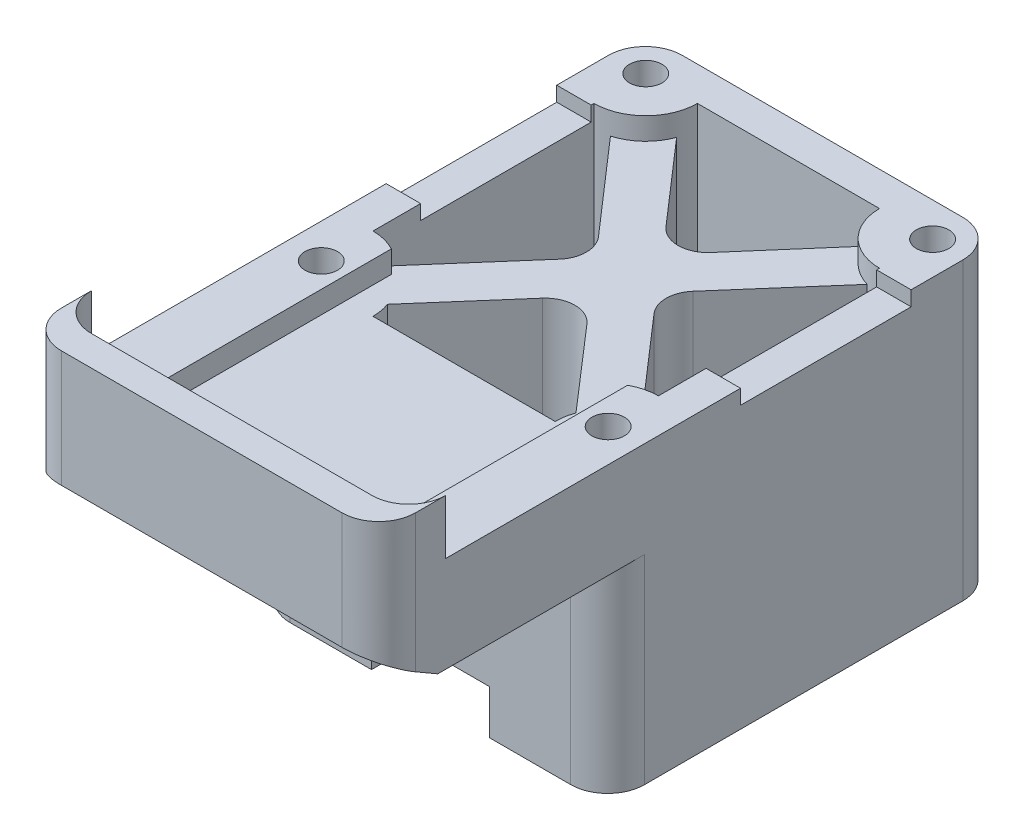
SolidWorks part; units mm, degrees
ref_plane "前视基准面" through (0, 0, 0) normal (0, 0, 1) x (1, 0, 0)
ref_plane "上视基准面" through (0, 0, 0) normal (0, 1, 0) x (1, 0, 0)
ref_plane "右视基准面" through (0, 0, 0) normal (1, 0, 0) x (0, 0, -1)
sketch "草图1" plane through (0, 0, 0) normal (0, 1, 0) x (1, 0, 0)
  line L0 (-18.2675, -0.0029) -> (18.255, -0.0029) construction
  line L2 (-9.5062, 13.2897) -> (9.4938, 13.2897)
  line L4 (-7.4272, 10.9831) -> (-1.4996, 4.1802)
  line L6 (-9.6723, 8.738) -> (-3.2009, 1.311)
  line L7 (-12.0062, 10.7897) -> (-12.0062, -10.7623)
  line L8 (-9.5062, -13.2623) -> (9.4938, -13.2623)
  line L9 (11.9938, 10.7897) -> (11.9938, -10.7623)
  line L10 (-12.0062, 13.2897) -> (11.9938, -13.2623) construction
  line L11 (-12.0062, -13.2623) -> (11.9938, 13.2897) construction
  line L12 (-9.6723, -8.7438) -> (-9.6723, 8.738)
  line L13 (-9.6723, -8.7438) -> (-3.2009, -1.3168)
  line L21 (-0.0062, -0.0029) -> (-0.0062, 21.7953) construction
  line L22 (-7.4272, 10.9831) -> (7.4147, 10.9831)
  line L23 (1.5194, 4.1838) -> (7.4147, 10.9831)
  line L24 (9.6598, -8.7438) -> (9.6598, 8.738)
  line L25 (9.6598, -8.7438) -> (3.1884, -1.3168)
  line L26 (9.6598, 8.738) -> (3.1884, 1.311)
  line L27 (1.5194, -4.1897) -> (7.4147, -10.9889)
  line L28 (-7.4272, -10.9889) -> (-1.4996, -4.186)
  line L29 (-7.4272, -10.9889) -> (7.4147, -10.9889)
  circle A0 centre (-9.6723, 10.9831) radius 1.1
  circle A1 centre (-9.6723, 10.9831) radius 2.2451
  circle A2 centre (9.7557, 10.9831) radius 1.1
  circle A4 centre (-9.6723, -10.9889) radius 1.1
  circle A5 centre (9.7557, -10.9889) radius 1.1
  circle A7 centre (-9.6723, -10.9889) radius 2.2451
  arc A8 (-12.0062, -10.7623) -> (-9.5062, -13.2623) centre (-9.5062, -10.7623) ccw
  arc A9 (9.4938, -13.2623) -> (11.9938, -10.7623) centre (9.4938, -10.7623) ccw
  arc A10 (11.9938, 10.7897) -> (9.4938, 13.2897) centre (9.4938, 10.7897) ccw
  arc A11 (-9.5062, 13.2897) -> (-12.0062, 10.7897) centre (-9.5062, 10.7897) ccw
  arc A12 (-3.2009, -1.3168) -> (-3.2009, 1.311) centre (-4.7088, -0.0029) ccw
  arc A16 (-6.1723, 10.9831) -> (-9.6723, 7.4831) centre (-9.6723, 10.9831) cw
  circle A17 centre (9.6598, 10.9831) radius 2.2451
  circle A18 centre (9.6598, -10.9889) radius 2.2451
  arc A19 (1.5194, 4.1838) -> (-1.4996, 4.1802) centre (0.0083, 5.494) cw
  arc A20 (3.1884, -1.3168) -> (3.1884, 1.311) centre (4.6963, -0.0029) cw
  arc A21 (1.5194, -4.1897) -> (-1.4996, -4.186) centre (0.0083, -5.4998) ccw
  arc A22 (6.1598, 10.9831) -> (9.6598, 7.4831) centre (9.6598, 10.9831) ccw
  arc A23 (6.1598, -10.9889) -> (9.6598, -7.4889) centre (9.6598, -10.9889) cw
  arc A24 (-6.1723, -10.9889) -> (-9.6723, -7.4889) centre (-9.6723, -10.9889) ccw
  point P5 (-0.0062, 0.0137)
  dimension "D5" = 2
  dimension "D6" = 2
  dimension "D1" = 24
  dimension "D2" = 26.552
  dimension "D3" = 19.428
  dimension "D4" = 21.972
extrude "凸台-拉伸1" add sketch "草图1" along normal blind 20 contours A22 L22 A16 L4 A19 L23 | L25 A23 L24 A22 L26 A20 | A24 L28 A21 L27 A23 L25 A20 L26 A22 L23 A19 L4 A16 L6 A12 L13 | A24 L13 A12 L6 A16 L12 | A24 L29 A23 L27 A21 L28 | L2 A10 L9 A9 L8 A8 L7 A11 region at (-0.0006, 0, -8.1687) region at (-0.0113, 0, 0.0029) region at (-7.1341, 0, 0.0029) region at (7.1216, 0, 0.0029) region at (-0.0006, 0, 8.1745)
extrude "凸台-拉伸2" add sketch "草图3<8>" along normal blind 18.5 contours A19 L4 A1 L6 A12 L13 A7 A21 A17 region at (-0.0113, 0, 0.0029)
sketch "草图3<8>" plane through (0, 0, 0) normal (0, 1, 0) x (1, 0, 0) same geometry as "草图1"
sketch "草图10" plane through (0, 20, 0) normal (0, 1, 0) x (1, 0, 0)
  line L1 (-12.0062, -28.7623) -> (11.9938, -28.7623)
  line L6 (-12.0062, -10.7623) -> (-12.0062, -28.7623)
  line L7 (11.9938, -10.7623) -> (11.9938, -28.7623)
  line L8 (-9.5062, -13.2623) -> (9.4938, -13.2623)
  arc A6 (-9.5062, -13.2623) -> (-12.0062, -10.7623) centre (-9.5062, -10.7623) cw
  arc A7 (9.4938, -13.2623) -> (11.9938, -10.7623) centre (9.4938, -10.7623) ccw
  dimension "D1" = 18
extrude "凸台-拉伸8" add sketch "草图10" against normal blind 6.5 contours L8 L1 region at (-0.0062, 20, 20.9528)
extrude "切除-拉伸1" cut sketch "草图3<6>" along normal blind 3 contours A19 L4 A1 L6 A12 L13 A7 A21 A17 region at (-0.0113, 0, 0.0029)
sketch "草图3<6>" plane through (0, 0, 0) normal (0, 1, 0) x (1, 0, 0) same geometry as "草图1"
sketch "草图8" plane through (0, 0, 13.2623) normal (0, 0, 1) x (1, 0, 0)
  line L0 (0, -1.8709) -> (0, 6.9394) construction
  line L1 (4, 3) -> (-4, 3)
  line L2 (-4, 3) -> (-4, 0)
  line L3 (-9.5062, 0) -> (9.4938, 0) construction
  line L4 (-4, 0) -> (4, 0)
  line L5 (4, 3) -> (4, 0)
  point P10 (0, 0)
  point P11 (0, 3)
  dimension "D1" = 4
  dimension "D2" = 3
extrude "切除-拉伸12" cut sketch "草图8" against normal up to next
extrude "切除-拉伸13" cut sketch "草图1<10>" along normal through all contours A0 | A2 | A5 | A4
sketch "草图1<10>" plane through (0, 0, 0) normal (0, 1, 0) x (1, 0, 0) same geometry as "草图1"
sketch "草图18" plane through (11.9938, 0, 0) normal (1, 0, 0) x (0, 0, -1)
  line L0 (10.7897, 20) -> (-28.7623, 20) construction
  line L1 (-4.2623, 20) -> (7.2897, 20)
  line L2 (-4.2623, 20) -> (-4.2623, 19)
  line L3 (-4.2623, 19) -> (7.2897, 19)
  line L4 (7.2897, 20) -> (7.2897, 19)
  line L5 (13.2897, 20) -> (13.2897, 0) construction
  line L6 (-13.2623, 13.5) -> (-13.2623, 0) construction
  dimension "D1" = 6
  dimension "D2" = 9
  dimension "D3" = 1
extrude "切除-拉伸16" cut sketch "草图18" against normal through all
chamfer "倒角1" distance 4 angle 30 1 edges at (-0.0062, 13.5, 28.7623) first distance on face at (-0.0062, 13.5, 17.7682)
sketch "草图20" plane through (0, 20, 0) normal (0, 1, 0) x (1, 0, 0)
  line L1 (-12.0062, -26.2623) -> (-12.0062, -28.7623)
  line L6 (-12.0062, -28.7623) -> (-9.5062, -28.7623)
  line L8 (11.9938, -26.2623) -> (11.9938, -28.7623)
  line L10 (11.9938, -28.7623) -> (9.4938, -28.7623)
  arc A2 (-9.5062, -28.7623) -> (-12.0062, -26.2623) centre (-9.5062, -26.2623) cw
  arc A3 (9.4938, -28.7623) -> (11.9938, -26.2623) centre (9.4938, -26.2623) ccw
  point P11 (-12.0062, -28.7623)
  point P12 (-12.0062, -28.7623)
  point P15 (11.9938, -28.7623)
  point P18 (11.9938, -28.7623)
  dimension "D1" = 2.5
  dimension "D2" = 2.5
extrude "切除-拉伸18" cut sketch "草图20" against normal up to next
sketch "草图21" plane through (0, 20, 0) normal (0, 1, 0) x (1, 0, 0)
  line L0 (-12.0062, -15.2623) -> (-12.0062, -24.2309)
  line L1 (-12.0062, -4.2623) -> (-12.0062, -26.2623) construction
  line L2 (-9.5062, -26.7309) -> (9.4938, -26.7309)
  line L3 (11.9938, -24.2309) -> (11.9938, -13.9209)
  line L4 (11.9938, -4.2623) -> (11.9938, -26.2623) construction
  line L6 (-6.1723, -10.9889) -> (6.1598, -10.9889) construction
  line L15 (-9.5062, -28.7623) -> (9.4938, -28.7623)
  line L16 (11.9938, -26.2623) -> (11.9938, -4.2623)
  line L17 (11.9938, -4.2623) -> (9.6598, -4.2623)
  line L18 (9.6598, -4.2623) -> (9.6598, -7.4889)
  line L19 (6.1598, -10.9889) -> (-6.1723, -10.9889)
  line L20 (-9.6723, -7.4889) -> (-9.6723, -4.2623)
  line L21 (-9.6723, -4.2623) -> (-12.0062, -4.2623)
  line L22 (-12.0062, -4.2623) -> (-12.0062, -26.2623)
  line L23 (-9.5062, -28.7623) -> (9.4938, -28.7623)
  line L24 (11.9938, -26.2623) -> (11.9938, -13.9209)
  line L30 (-12.0062, -15.2623) -> (-12.0062, -26.2623)
  arc A0 (11.9938, -24.2309) -> (9.4938, -26.7309) centre (9.4938, -24.2309) cw
  arc A1 (-9.5062, -26.7309) -> (-12.0062, -24.2309) centre (-9.5062, -24.2309) cw
  arc A6 (-12.0062, -26.2623) -> (-9.5062, -28.7623) centre (-9.5062, -26.2623) ccw
  arc A7 (9.4938, -28.7623) -> (11.9938, -26.2623) centre (9.4938, -26.2623) ccw
  arc A8 (9.6598, -7.4889) -> (6.1598, -10.9889) centre (9.6598, -10.9889) ccw
  arc A9 (-6.1723, -10.9889) -> (-9.6723, -7.4889) centre (-9.6723, -10.9889) ccw
  arc A10 (-12.0062, -26.2623) -> (-9.5062, -28.7623) centre (-9.5062, -26.2623) ccw
  arc A11 (9.4938, -28.7623) -> (11.9938, -26.2623) centre (9.4938, -26.2623) ccw
  arc M2 (-12.0062, -26.2623) -> (-9.5062, -28.7623) centre (-9.5062, -26.2623) ccw
  line M3 (-9.5062, -28.7623) -> (9.4938, -28.7623)
  arc M4 (9.4938, -28.7623) -> (11.9938, -26.2623) centre (9.4938, -26.2623) ccw
  line M5 (11.9938, -26.2623) -> (11.9938, -4.2623)
  line M13 (-12.0062, -4.2623) -> (-12.0062, -26.2623)
  dimension "D2" = 2.5
  dimension "D1" = 15.742
  dimension "D3" = 0
sketch "草图22" plane through (0, 0, 10.9889) normal (0, 0, -1) x (-1, 0, 0)
  line L0 (9.5062, 20) -> (-9.4938, 20) construction
  line L1 (-7.9938, 20) -> (8.0062, 20)
  line L2 (-7.9938, 20) -> (-7.9938, 18.5)
  line L3 (-7.9938, 18.5) -> (8.0062, 18.5)
  line L4 (8.0062, 20) -> (8.0062, 18.5)
  line L5 (-11.9938, 20) -> (-11.9938, 0) construction
  line L6 (12.0062, 20) -> (12.0062, 0) construction
  dimension "D1" = 1.5
  dimension "D2" = 4
  dimension "D3" = 4
extrude "凸台-拉伸9" add sketch "草图21" along normal blind 3.7 contours L2 A1 A0 M13 M2 M3 M4 M5 region at (-0.0062, 20, 27.6348)
extrude "切除-拉伸19" cut sketch "草图22" against normal up to surface (15.742 mm away) and the other way blind 11.5 up to face at (-0.0062, 21.85, 26.7309)
